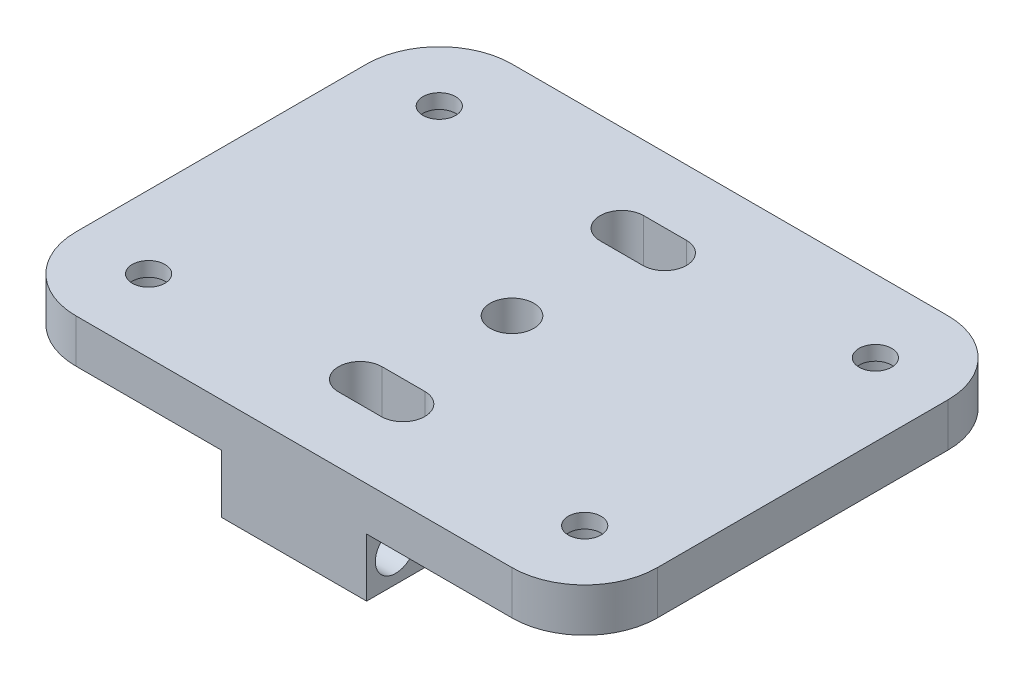
SolidWorks part; units mm, degrees
ref_plane "Plan de face" through (0, 0, 0) normal (0, 0, 1) x (1, 0, 0)
ref_plane "Plan de dessus" through (0, 0, 0) normal (0, 1, 0) x (1, 0, 0)
ref_plane "Plan de droite" through (0, 0, 0) normal (1, 0, 0) x (0, 0, -1)
sketch "Esquisse1" plane through (0, 0, 0) normal (0, 1, 0) x (1, 0, 0)
  line L0 (30, 20) -> (-35.7533, -23.8355) construction
  line L1 (-30, 30) -> (30, 30)
  line L2 (-40, 20) -> (-40, -20)
  line L3 (-30, -30) -> (30, -30)
  line L4 (40, 20) -> (40, -20)
  line L5 (-29.1047, 30) -> (-9.1047, 30)
  line L7 (-29.1047, -30) -> (-9.1047, -30)
  line L9 (-30, 20) -> (30, -20) construction
  arc A0 (-30, 30) -> (-40, 20) centre (-30, 20) ccw
  arc A1 (-40, -20) -> (-30, -30) centre (-30, -20) ccw
  arc A2 (30, -30) -> (40, -20) centre (30, -20) ccw
  arc A3 (30, 30) -> (40, 20) centre (30, 20) cw
  circle A4 centre (-30, 20) radius 2.25
  circle A5 centre (30, 20) radius 2.25
  circle A6 centre (-30, -20) radius 2.25
  circle A7 centre (30, -20) radius 2.25
  circle A8 centre (0, 0) radius 3
  point P7 (-40, 30)
  point P12 (40, -30)
  point P15 (40, 30)
  dimension "D3" = 10
  dimension "D4" = 6
  dimension "D5" = 4.5
  dimension "D1" = 80
  dimension "D2" = 60
extrude "Boss.-Extru.3" add sketch "Esquisse1" along normal blind 6 contours A3 L1 A0 L2 A1 L3 A2 L4 A8 A7 A6 A5 A4 region at (-29.5524, 0, -29)
sketch "Esquisse2" plane through (0, 0, 0) normal (0, -1, 0) x (1, 0, 0)
  line L0 (-30, 30) -> (30, 30) construction
  line L1 (-10, 30) -> (10, 30)
  line L2 (-10, 30) -> (-10, -30)
  line L3 (-10, -30) -> (10, -30)
  line L4 (10, 30) -> (10, -30)
  line L5 (-30, -30) -> (30, -30) construction
  line L6 (-40, -20) -> (-40, 20) construction
  circle A4 centre (0, 0) radius 3 construction
  circle A5 centre (0, 0) radius 3
  dimension "D1" = 20
  dimension "D2" = 30
extrude "Boss.-Extru.4" add sketch "Esquisse2" along normal blind 8
sketch "Esquisse3" plane through (0, 0, 0) normal (0, -1, 0) x (1, 0, 0)
  line L0 (-30, 20) -> (30, -20) construction
  line L1 (-30, -20) -> (30, 20) construction
  circle A0 centre (-30, 20) radius 4
  circle A1 centre (-30, -20) radius 4
  circle A2 centre (30, 20) radius 4
  circle A3 centre (30, -20) radius 4
extrude "Enlèv. mat.-Extru.2" cut sketch "Esquisse3" against normal blind 4
sketch "Esquisse7" plane through (-10, 0, 0) normal (-1, 0, 0) x (0, 0, 1)
  line L0 (26, -3.8774) -> (-26, -3.8774) construction
  line L1 (30, -8) -> (30, 0) construction
  line L3 (-30, -8) -> (-30, 0) construction
  line L4 (30, -8) -> (-30, -8) construction
  circle A2 centre (26, -3.8774) radius 2.8
  circle A3 centre (-26, -3.8774) radius 2.8
  dimension "D1" = 5.6
  dimension "D2" = 4
  dimension "D3" = 4.1226
  dimension "D4" = 4
extrude "Enlèv. mat.-Extru.8" cut sketch "Esquisse7" against normal blind 8.1
sketch "Esquisse8" plane through (0, -8, 0) normal (0, -1, 0) x (1, 0, 0)
  line L0 (-2.8795, 18) -> (3, 18) construction
  line L1 (-2.8795, 21) -> (3, 21)
  line L2 (-2.8795, 15) -> (3, 15)
  line L3 (-2.8795, -18) -> (3, -18) construction
  line L4 (-2.8795, -15) -> (3, -15)
  line L5 (-2.8795, -21) -> (3, -21)
  line L6 (10, 30) -> (-10, 30) construction
  line L7 (-10, -30) -> (10, -30) construction
  line L9 (10, -30) -> (10, 30) construction
  line L10 (-10, 30) -> (-10, -30) construction
  arc A0 (-2.8795, 21) -> (-2.8795, 15) centre (-2.8795, 18) ccw
  arc A1 (3, 15) -> (3, 21) centre (3, 18) ccw
  arc A2 (-2.8795, -15) -> (-2.8795, -21) centre (-2.8795, -18) ccw
  arc A3 (3, -21) -> (3, -15) centre (3, -18) ccw
  point P2 (0.0602, 18)
  point P7 (0.0602, -18)
  point P22 (0, 20)
  point P23 (0, 0)
  dimension "D1" = 12
  dimension "D3" = 7
  dimension "D4" = 7
  dimension "D6" = 7.1205
  dimension "D2" = 12
  dimension "D5" = 6
extrude "Enlèv. mat.-Extru.9" cut sketch "Esquisse8" against normal through all
sketch "Esquisse9" plane through (10, 0, 0) normal (1, 0, 0) x (0, 0, -1)
  line L0 (-30, -8) -> (-30, 0) construction
  line L1 (30, -8) -> (30, 0) construction
  line L3 (-26, -3.88) -> (26, -3.88) construction
  line L5 (30, -8) -> (-30, -8) construction
  circle A0 centre (-26, -3.88) radius 2.8
  circle A1 centre (26, -3.88) radius 2.8
  dimension "D1" = 5.6
  dimension "D2" = 4
  dimension "D3" = 4
  dimension "D4" = 4.12
  dimension "D5" = 4.12
extrude "Enlèv. mat.-Extru.10" cut sketch "Esquisse9" against normal blind 8.1
